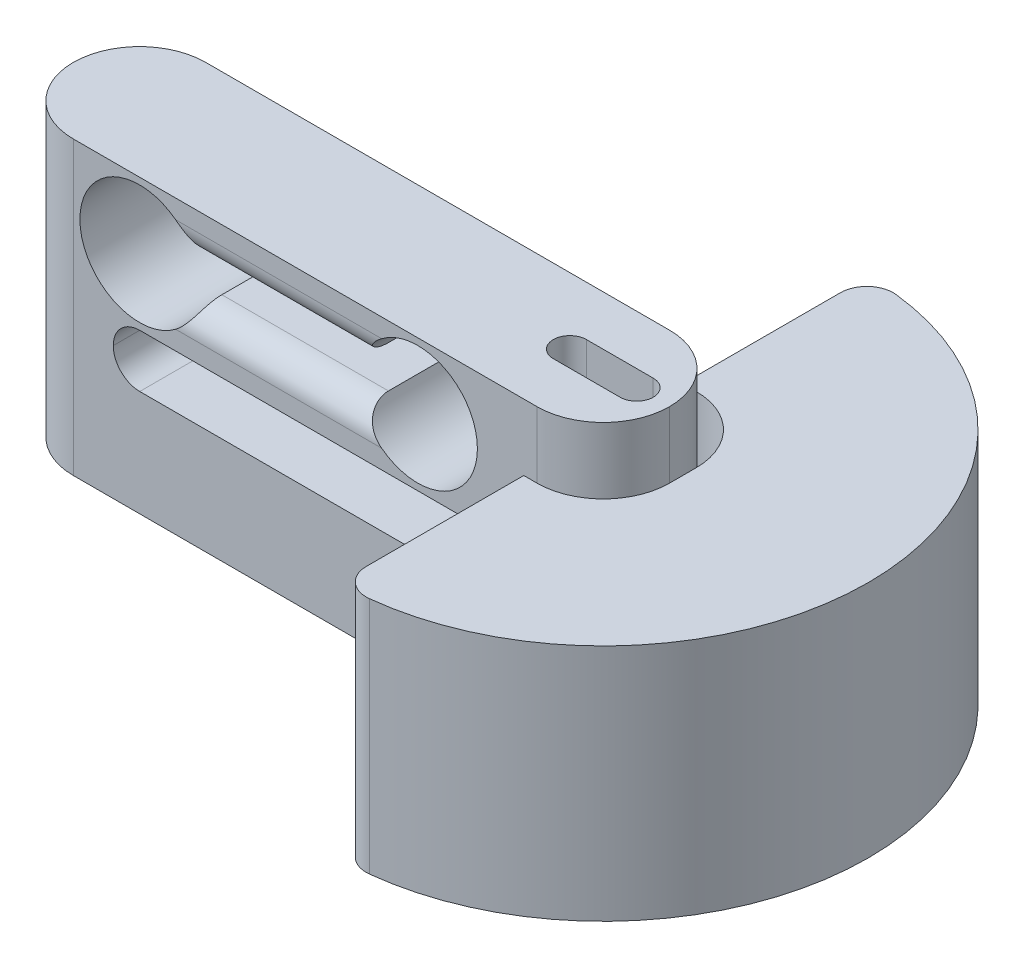
SolidWorks part; units mm, degrees
ref_plane "Front Plane" through (0, 0, 0) normal (0, 0, 1) x (1, 0, 0)
ref_plane "Top Plane" through (0, 0, 0) normal (0, 1, 0) x (1, 0, 0)
ref_plane "Right Plane" through (0, 0, 0) normal (1, 0, 0) x (0, 0, -1)
other "Center of Mass"
sketch "Sketch1" plane through (0, 0, 0) normal (0, 0, 1) x (1, 0, 0)
  line L0 (5, 0) -> (0, 0)
  line L1 (0, 0) -> (-5, 0)
  line L2 (-5, 0) -> (-35, 0)
  line L3 (5, 0) -> (5, -10)
  line L4 (5, -10) -> (-5, -10)
  line L5 (-5, -10) -> (-31.9826, -10)
  line L6 (-35, 0) -> (-40, 0)
  line L7 (-26.8791, -3.4207) -> (-11.5008, -3.4207)
  line L8 (-26.8791, -3.4207) -> (-26.8791, -6.5793)
  line L9 (-26.8791, -6.5793) -> (-11.5008, -6.5793)
  line L10 (-11.5008, -3.4207) -> (-11.5008, -6.5793)
  line L11 (-26.8791, -3.4207) -> (-11.5008, -6.5793) construction
  line L12 (-26.8791, -6.5793) -> (-11.5008, -3.4207) construction
  line L13 (-40, 0) -> (-40, -14)
  line L14 (-40, -14) -> (-31.9826, -14)
  line L15 (-31.9826, -14) -> (-31.9826, -10)
  circle A0 centre (-30, -5) radius 4.5
  circle A1 centre (-9, -5) radius 4.5
  point P12 (-19.1899, -5)
  dimension "D5" = 5
  dimension "D6" = 5
  dimension "D7" = 9
  dimension "D8" = 9
  dimension "D1" = 5
  dimension "D2" = 5
  dimension "D3" = 30
  dimension "D4" = 10
  dimension "D9" = 4
  dimension "D10" = 40
  dimension "D11" = 14
extrude "Boss-Extrude1" add sketch "Sketch1" along normal blind 5 and the other way blind 5 contours L14 L15 L5 L4 L3 L0 L1 L2 L6 L13 A1 L9 A0 L7 region at (4.5287, -5, 0)
sketch "Sketch2" plane through (0, 0, 0) normal (0, 1, 0) x (1, 0, 0)
  line L0 (-2.521, 0) -> (2.521, 0) construction
  line L1 (-2.521, 1.25) -> (2.521, 1.25)
  line L2 (-2.521, -1.25) -> (2.521, -1.25)
  arc A0 (-2.521, 1.25) -> (-2.521, -1.25) centre (-2.521, 0) ccw
  arc A1 (2.521, -1.25) -> (2.521, 1.25) centre (2.521, 0) ccw
  point P2 (0, 0)
extrude "Cut-Extrude1" cut sketch "Sketch2" against normal blind 5
sketch "Sketch3" plane through (0, 0, 0) normal (0, 1, 0) x (1, 0, 0)
  line L0 (5, -5) -> (-40, -5) construction
  line L1 (-40, 5) -> (5.8816, 5)
  line L2 (-40, 5) -> (-40, -5)
  line L3 (-40, -5) -> (5.8816, -5)
  line L4 (5.8816, 5) -> (5.8816, -5)
  line L6 (-44.7352, 22.5342) -> (0, 22.5342)
  line L7 (-44.7352, 22.5342) -> (-44.7352, -27.8282)
  line L8 (-44.7352, -27.8282) -> (0, -27.8282)
  line L9 (0, 22.5342) -> (0, -27.8282)
  circle A0 centre (0, 0) radius 20
  dimension "D1" = 40
extrude "Boss-Extrude2" add sketch "Sketch3" against normal blind 8 from offset 14 contours L9 A0 L1 L4 L3 | L1 L9 L3 L4 | L1 A0 L3 L9 | A0 L1 L2 L3 region at (-29.894, 0, 0) region at (-9.8957, 0, 0) region at (9.0612, 0, 0) region at (2.9408, 0, 0) offset against normal yes
sketch "Sketch4" plane through (0, -14, 0) normal (0, 1, 0) x (1, 0, 0)
  line L0 (5, 5) -> (-40, 5) construction
  line L1 (0, 20) -> (46.8504, 20)
  line L2 (0, 20) -> (0, -35.9681)
  line L3 (0, -35.9681) -> (46.8504, -35.9681)
  line L4 (46.8504, 20) -> (46.8504, -35.9681)
  line L5 (6, 6) -> (-6.1468, 6)
  line L6 (6, 6) -> (6, -6)
  line L7 (6, -6) -> (-6.1468, -6)
  line L8 (-6.1468, 6) -> (-6.1468, -6)
  line L9 (5, -5) -> (-40, -5) construction
  line L10 (5, 5) -> (5, -5) construction
  circle A0 centre (0, 0) radius 20
  arc M8 (0, -20) -> (0, 20) centre (0, 0) ccw
  line M9 (0, 20) -> (0, 5)
  dimension "D4" = 40
  dimension "D1" = 1
  dimension "D2" = 1
  dimension "D3" = 1
extrude "Boss-Extrude3" add sketch "Sketch4" along normal blind 10 contours L6 L7 L2 L5 M8 M9 region at (9.1986, -14, 0)
fillet "Fillet2" radius 5 6 edges at (-40, -11, -5) (-40, -11, 5) (6, -9, 6) (6, -9, -6) (5, -5, 5) (5, -5, -5)
fillet "Fillet3" radius 2 8 edges at (-19.5, -3.4207, -5) (-19.5, -6.5793, -5) (-19.5, -6.5793, 5) (-19.5, -3.4207, 5) (-31.9826, -10, 0) (-31.9826, -14, 0) (0, -13, -20) (0, -13, 20)
sketch "Sketch5" plane through (0, -22, 0) normal (0, -1, 0) x (1, 0, 0)
  line L0 (-35, 0) -> (-12, 0) construction
  line L1 (-35, 3.25) -> (-12, 3.25)
  line L2 (-35, -3.25) -> (-12, -3.25)
  line L4 (-6.5, 1.5) -> (-3.5, 1.5)
  line L5 (-6.5, 1.5) -> (-6.5, -1.5)
  line L6 (-6.5, -1.5) -> (-3.5, -1.5)
  line L7 (-3.5, 1.5) -> (-3.5, -1.5)
  line L8 (-6.5, 1.5) -> (-3.5, -1.5) construction
  line L9 (-6.5, -1.5) -> (-3.5, 1.5) construction
  line L10 (3.5, 1.5) -> (6.5, 1.5)
  line L11 (3.5, 1.5) -> (3.5, -1.5)
  line L12 (3.5, -1.5) -> (6.5, -1.5)
  line L13 (6.5, 1.5) -> (6.5, -1.5)
  line L14 (3.5, 1.5) -> (6.5, -1.5) construction
  line L15 (3.5, -1.5) -> (6.5, 1.5) construction
  arc A0 (-35, 3.25) -> (-35, -3.25) centre (-35, 0) ccw
  arc A1 (-12, -3.25) -> (-12, 3.25) centre (-12, 0) ccw
  circle A3 centre (0, 0) radius 2
  point P3 (-23.5, 0)
  point P8 (-5, 0)
  point P13 (5, 0)
  dimension "D3" = 3
  dimension "D9" = 4
  dimension "D1" = 35
  dimension "D2" = 12
  dimension "D4" = 3
  dimension "D5" = 0
  dimension "D6" = 5
  dimension "D7" = 3
  dimension "D8" = 5
extrude "Cut-Extrude2" cut sketch "Sketch5" against normal blind 4
fillet "Fillet4" radius 1 7 edges at (-23.5, -18, 3.25) (-8.75, -18, 0) (-23.5, -18, -3.25) (-38.25, -18, 0) (0, -18, -5) (0, -18, 5) (0, -22, -2)
sketch "Sketch6" plane through (0, -22, 0) normal (0, -1, 0) x (1, 0, 0)
  circle A0 centre (-35, 0) radius 3.25
extrude "Cut-Extrude3" cut sketch "Sketch6" against normal blind 5
sketch "Sketch7" plane through (0, 0, 0) normal (0, 1, 0) x (1, 0, 0)
  circle A0 centre (0, 0) radius 2
extrude "Boss-Extrude4" add sketch "Sketch7" along normal blind 3.7 from surface starting at face at (-4.548, -14, 0)
fillet "Fillet5" radius 1.6 2 edges at (0, -14, 2) (0, -10.3, 2)
